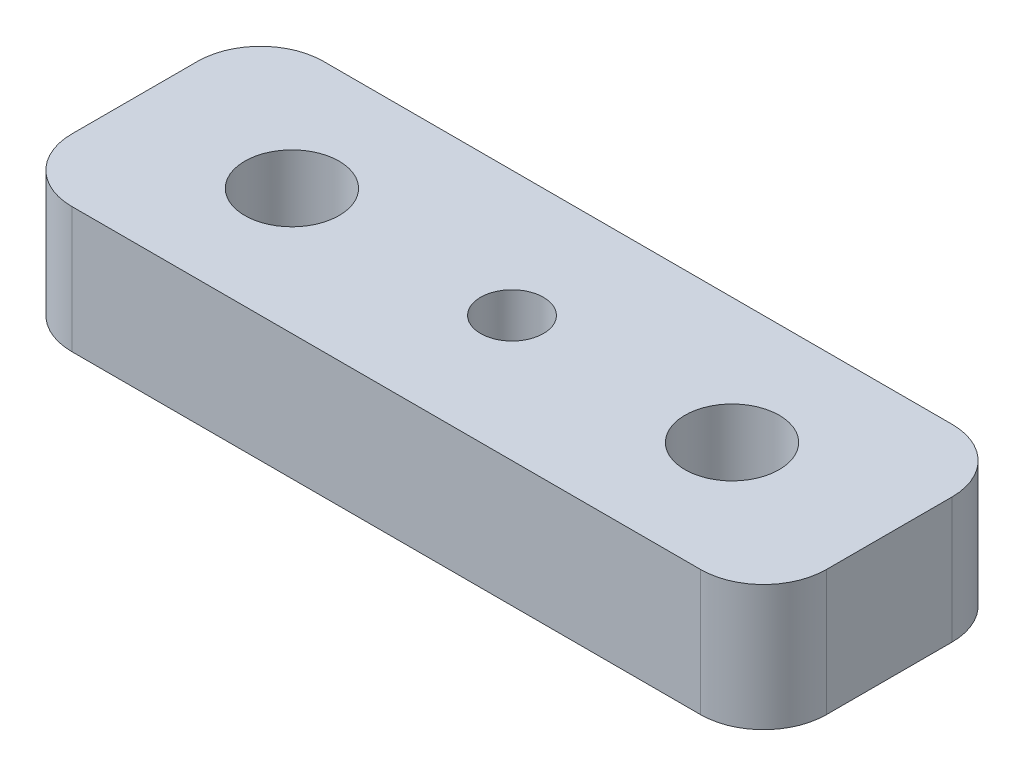
SolidWorks part; units mm, degrees
ref_plane "Front Plane" through (0, 0, 0) normal (0, 0, 1) x (1, 0, 0)
ref_plane "Top Plane" through (0, 0, 0) normal (0, 1, 0) x (1, 0, 0)
ref_plane "Right Plane" through (0, 0, 0) normal (1, 0, 0) x (0, 0, -1)
sketch "Sketch1" plane through (0, 0, 0) normal (0, 1, 0) x (1, 0, 0)
  line L0 (0, 4) -> (10, 4)
  line L1 (12, 2) -> (12, -2)
  line L2 (10, -4) -> (0, -4)
  line L3 (0, -4) -> (-10, -4)
  line L4 (-12, -2) -> (-12, 2)
  line L5 (-10, 4) -> (0, 4)
  line L6 (0, -55) -> (0, 55) construction
  circle A0 centre (0, 0) radius 4 construction
  circle A1 centre (0, 0) radius 1
  arc A2 (10, -4) -> (12, -2) centre (10, -2) ccw
  arc A3 (12, 2) -> (10, 4) centre (10, 2) ccw
  arc A4 (-10, -4) -> (-12, -2) centre (-10, -2) cw
  arc A5 (-10, 4) -> (-12, 2) centre (-10, 2) ccw
  circle A6 centre (0, 0) radius 2.5
  circle A7 centre (-7, 0) radius 1.5
  circle A8 centre (-7, 0) radius 2.5
  circle A9 centre (7, 0) radius 2.5
  circle A10 centre (7, 0) radius 1.5
  point P14 (12, 4)
  point P19 (-12, 4)
  dimension "D1" = 2
  dimension "D2" = 8
  dimension "D5" = 2
  dimension "D6" = 5
  dimension "D7" = 3
  dimension "D8" = 5
  dimension "D3" = 12
  dimension "D4" = 12
  dimension "D9" = 5
  dimension "D10" = 4
  dimension "D11" = 14
extrude "Boss-Extrude1" add sketch "Sketch1" along normal blind 4 contours L3 A4 L4 A5 L5 L0 A3 L1 A2 L2
extrude "Cut-Extrude1" cut sketch "Sketch1<3>" along normal up to next contours A1 | A7 | A10
sketch "Sketch1<3>" plane through (0, 0, 0) normal (0, 1, 0) x (1, 0, 0) same geometry as "Sketch1"
extrude "Cut-Extrude2" cut sketch "Sketch1<4>" along normal blind 2 contours A6
sketch "Sketch1<4>" plane through (0, 0, 0) normal (0, 1, 0) x (1, 0, 0) same geometry as "Sketch1"
